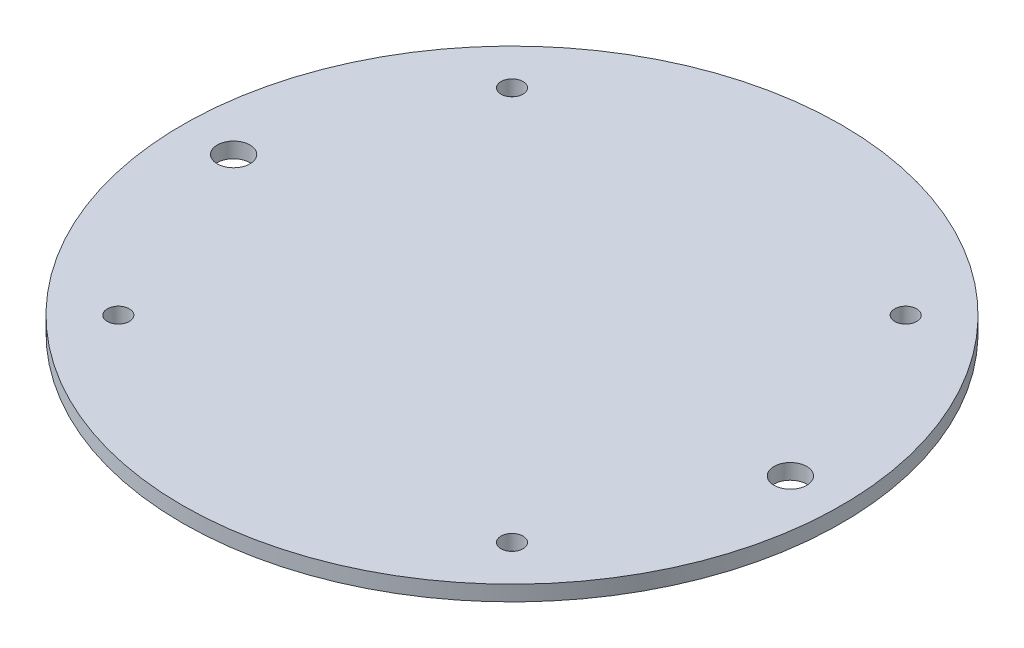
SolidWorks part; units mm, degrees
ref_plane "Front Plane" through (0, 0, 0) normal (0, 0, 1) x (1, 0, 0)
ref_plane "Top Plane" through (0, 0, 0) normal (0, 1, 0) x (1, 0, 0)
ref_plane "Right Plane" through (0, 0, 0) normal (1, 0, 0) x (0, 0, -1)
sketch "Sketch1" plane through (0, 0, 0) normal (0, 1, 0) x (1, 0, 0)
  circle A0 centre (0, 0) radius 64.4
  dimension "Diameter" = 128.8
extrude "Boss-Extrude1" add sketch "Sketch1" along normal mid plane 3
sketch "Sketch2" plane through (0, 1.5, 0) normal (0, 1, 0) x (1, 0, 0)
  line L0 (-54.4, 0) -> (54.4, 0) construction
  point P2 (0, 0)
  dimension "RodDistance" = 108.8
hole_wizard "M6 Clearance Hole1" positions "Sketch3" profile "Sketch4" hole size "M6" standard "ANSI Metric" end condition up to next
sketch "Sketch3" plane through (0, 1.5, 0) normal (0, 1, 0) x (1, 0, 0)
  point P0 (-54.4, 0)
  point P3 (54.4, 0)
sketch "Sketch4" plane through (-54.4, 1.5, 0) normal (1, 0, 0) x (0, 0, 1)
  line L0 (0, 0) -> (0, 3)
  line L1 (0, 3) -> (3.2, 3)
  line L2 (3.2, 3) -> (3.2, 0)
  line L5 (3.2, 0) -> (0, 0)
  line L11 (0, -6.35) -> (0, 107.95) construction
  dimension "Thru Hole Dia." = 6.4
  dimension "Thru Hole Depth" = 3
sketch "Sketch5" plane through (0, 1.5, 0) normal (0, 1, 0) x (1, 0, 0)
  line L0 (0, 0) -> (64.4, 0) construction
  line L2 (0, 0) -> (38.4666, 38.4666) construction
  circle A0 centre (0, 0) radius 64.4 construction
  dimension "D1" = 45
  dimension " NoseShellHoleRadius" = 54.4
hole_wizard "M4 Clearance Hole1" positions "Sketch6" profile "Sketch7" hole size "M4" standard "ANSI Metric" end condition up to next
sketch "Sketch6" plane through (0, 1.5, 0) normal (0, 1, 0) x (1, 0, 0)
  point P0 (38.4666, 38.4666)
sketch "Sketch7" plane through (38.4666, 1.5, -38.4666) normal (1, 0, 0) x (0, 0, 1)
  line L0 (0, 0) -> (0, 3)
  line L1 (0, 3) -> (2.15, 3)
  line L2 (2.15, 3) -> (2.15, 0)
  line L5 (2.15, 0) -> (0, 0)
  line L11 (0, -6.35) -> (0, 107.95) construction
  dimension "Thru Hole Dia." = 4.3
  dimension "Thru Hole Depth" = 3
pattern_circular "CirPattern1" count 4 over 360 about axis through (0, 1.5, 0) along (0, -1, 0) of "M4 Clearance Hole1" reverse direction yes
